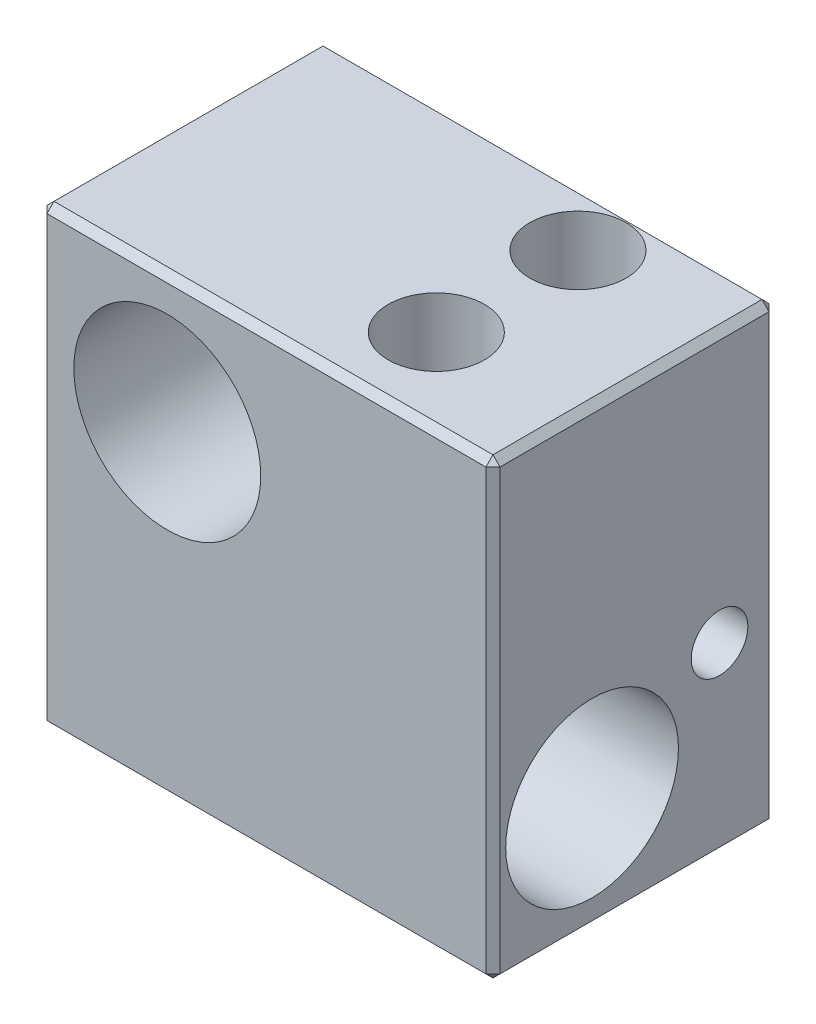
SolidWorks part; units mm, degrees
material "3.1325 (EN-AW 2017A)"
ref_plane "Plan de face" through (0, 0, 0) normal (0, 0, 1) x (1, 0, 0)
ref_plane "Plan de dessus" through (0, 0, 0) normal (0, 1, 0) x (1, 0, 0)
ref_plane "Plan de droite" through (0, 0, 0) normal (1, 0, 0) x (0, 0, -1)
sketch "Esquisse1" plane through (0, 0, 0) normal (0, 0, 1) x (1, 0, 0)
  line L1 (0, 0) -> (16, 0)
  line L2 (0, 0) -> (0, 16)
  line L3 (0, 16) -> (16, 16)
  line L4 (16, 0) -> (16, 16)
  dimension "D1" = 16
  dimension "D2" = 16
extrude "Boss.-Extru.1" add sketch "Esquisse1" along normal blind 10
sketch "Esquisse2" plane through (0, 0, 10) normal (0, 0, 1) x (1, 0, 0)
  line L0 (16, 16) -> (0, 16) construction
  line L2 (0, 16) -> (0, 0) construction
  circle A0 centre (4.5, 11.5) radius 3
  dimension "D1" = 6
  dimension "D2" = 4.5
  dimension "D3" = 4.5
hole_wizard "Dégagement M61" positions "Esquisse4" profile "Esquisse3" hole size "M6" standard "ISO" end condition through all
sketch "Esquisse4" plane through (0, 0, 10) normal (0, 0, 1) x (1, 0, 0)
  point P0 (4.5, 11.5)
sketch "Esquisse3" plane through (4.5, 11.5, 10) normal (1, 0, 0) x (0, -1, 0)
  line L0 (0, 0) -> (0, 10)
  line L1 (0, 10) -> (3.3, 10)
  line L2 (3.3, 10) -> (3.3, 0)
  line L5 (3.3, 0) -> (0, 0)
  line L11 (0, -6.35) -> (0, 107.95) construction
  dimension "Diamètre du perçage jusqu'au prochain" = 6.6
  dimension "Profondeur du perçage jusqu'au prochain" = 10
sketch "Esquisse5" plane through (16, 0, 0) normal (1, 0, 0) x (0, 0, -1)
  line L0 (-10, 0) -> (0, 0) construction
  line L1 (-10, 0) -> (-10, 16) construction
  line L2 (0, 0) -> (0, 16) construction
  circle A0 centre (-6.5, 4) radius 3
  circle A1 centre (-2, 6.5) radius 1.5
  dimension "D1" = 6
  dimension "D2" = 3
  dimension "D3" = 4
  dimension "D4" = 3.5
  dimension "D5" = 2
  dimension "D6" = 6.5
hole_wizard "Diamètre du perçage Ø6.1 (6.1)1" positions "Esquisse7" profile "Esquisse6" hole size "Ø6.1" standard "ISO" end condition through all
sketch "Esquisse7" plane through (16, 0, 0) normal (1, 0, 0) x (0, 0, -1)
  point P0 (-6.5, 4)
sketch "Esquisse6" plane through (16, 4, 6.5) normal (0, 1, 0) x (0, 0, -1)
  line L0 (0, 0) -> (0, 16)
  line L1 (0, 16) -> (3.05, 16)
  line L2 (3.05, 16) -> (3.05, 0)
  line L5 (3.05, 0) -> (0, 0)
  line L11 (0, -6.35) -> (0, 107.95) construction
  dimension "Diamètre du perçage jusqu'au prochain" = 6.1
  dimension "Profondeur du perçage jusqu'au prochain" = 16
hole_wizard "Diamètre du perçage Ø2.0 (2)1" positions "Esquisse9" profile "Esquisse8" hole size "Ø2.0" standard "ISO" end condition through all
sketch "Esquisse9" plane through (16, 0, 0) normal (1, 0, 0) x (0, 0, -1)
  point P0 (-2, 6.5)
sketch "Esquisse8" plane through (16, 6.5, 2) normal (0, 1, 0) x (0, 0, -1)
  line L0 (0, 0) -> (0, 16)
  line L1 (0, 16) -> (1, 16)
  line L2 (1, 16) -> (1, 0)
  line L5 (1, 0) -> (0, 0)
  line L11 (0, -6.35) -> (0, 107.95) construction
  dimension "Diamètre du perçage jusqu'au prochain" = 2
  dimension "Profondeur du perçage jusqu'au prochain" = 16
sketch "Esquisse10" plane through (0, 16, 0) normal (0, 1, 0) x (1, 0, 0)
  line L0 (16, -10) -> (16, 0) construction
  line L1 (16, -10) -> (0, -10) construction
  line L2 (16, 0) -> (0, 0) construction
  circle A0 centre (11, -7) radius 1.5
  circle A1 centre (11, -2) radius 1.5
  dimension "D1" = 3
  dimension "D2" = 3
  dimension "D3" = 5
  dimension "D4" = 5
  dimension "D5" = 3
  dimension "D6" = 2
hole_wizard "Dégagement M31" positions "Esquisse14" profile "Esquisse13" hole size "M3" standard "ISO"
sketch "Esquisse14" plane through (0, 16, 0) normal (0, 1, 0) x (1, 0, 0)
  point P0 (11, -7)
sketch "Esquisse13" plane through (11, 16, 7) normal (1, 0, 0) x (0, 0, 1)
  line L0 (0, 0) -> (0, 12.0215)
  line L1 (0, 12.0215) -> (1.7, 11)
  line L2 (1.7, 11) -> (1.7, 0)
  line L5 (1.7, 0) -> (0, 0)
  line L10 (0, 12.0215) -> (-1.7, 11) construction
  line L11 (0, -6.35) -> (0, 107.95) construction
  dimension "Diamètre du perçage" = 3.4
  dimension "Profondeur du perçage" = 11
  dimension "Angle de pointe" = 118
hole_wizard "Dégagement M32" positions "Esquisse16" profile "Esquisse15" hole size "M3" standard "ISO"
sketch "Esquisse16" plane through (0, 16, 0) normal (0, 1, 0) x (1, 0, 0)
  point P0 (11, -2)
sketch "Esquisse15" plane through (11, 16, 2) normal (1, 0, 0) x (0, 0, 1)
  line L0 (0, 0) -> (0, 10.0215)
  line L1 (0, 10.0215) -> (1.7, 9)
  line L2 (1.7, 9) -> (1.7, 0)
  line L5 (1.7, 0) -> (0, 0)
  line L10 (0, 10.0215) -> (-1.7, 9) construction
  line L11 (0, -6.35) -> (0, 107.95) construction
  dimension "Diamètre du perçage" = 3.4
  dimension "Profondeur du perçage" = 9
  dimension "Angle de pointe" = 118
chamfer "Chanfrein1" distance 0.25 angle 45 12 edges at (0, 8, 0) (0, 8, 10) (8, 0, 10) (0, 0, 5) (8, 0, 0) (16, 8, 10) (16, 0, 5) (16, 8, 0) (8, 16, 10) (16, 16, 5) (8, 16, 0) (0, 16, 5)
